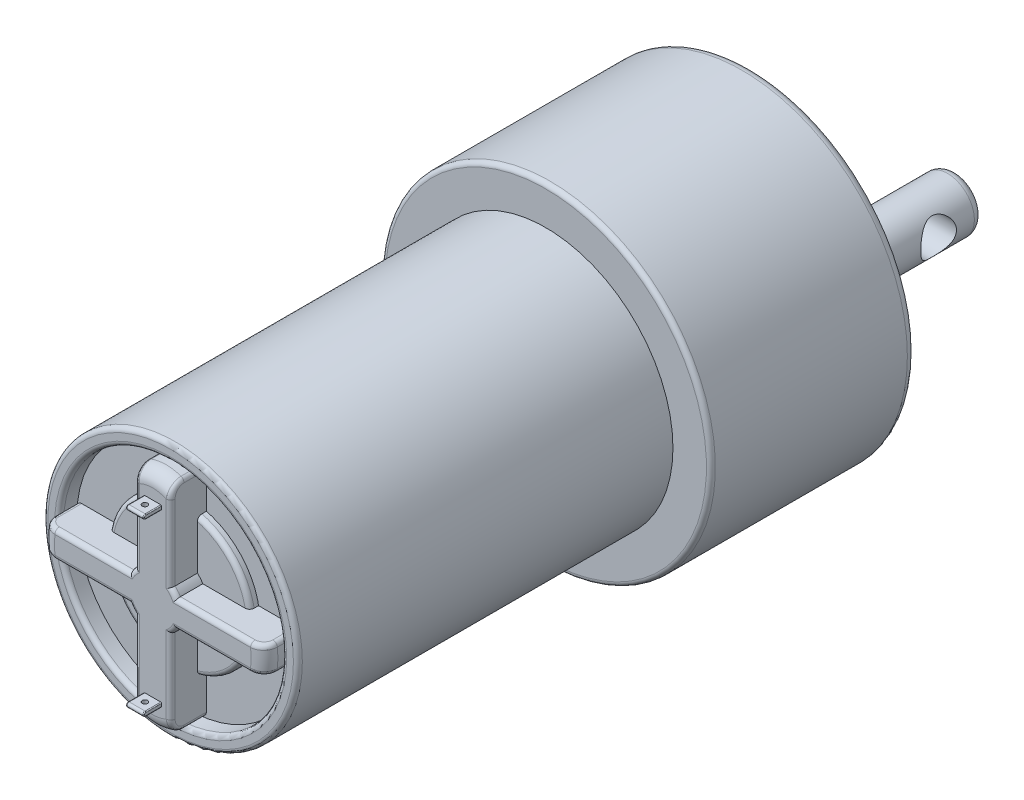
SolidWorks part; units mm, degrees
ref_plane "Front Plane" through (0, 0, 0) normal (0, 0, 1) x (1, 0, 0)
ref_plane "Top Plane" through (0, 0, 0) normal (0, 1, 0) x (1, 0, 0)
ref_plane "Right Plane" through (0, 0, 0) normal (1, 0, 0) x (0, 0, -1)
sketch "Sketch1" plane through (0, 0, 0) normal (0, 0, 1) x (1, 0, 0)
  circle A0 centre (0, 0) radius 14.25
  dimension "D1" = 28.5
extrude "Boss-Extrude1" add sketch "Sketch1" along normal blind 63
sketch "Sketch2" plane through (0, 0, 0) normal (0, 0, -1) x (-1, 0, 0)
  circle A0 centre (0, 0) radius 18.5
  dimension "D1" = 37
extrude "Boss-Extrude2" add sketch "Sketch2" against normal blind 23
sketch "Sketch3" plane through (0, 0, 0) normal (0, 0, -1) x (-1, 0, 0)
  line L0 (0, 0) -> (0, -6)
  line L1 (0, 20.35) -> (0, -20.35) construction
  circle A0 centre (0, -6) radius 6
  dimension "D1" = 6
extrude "Boss-Extrude6" add sketch "Sketch3" along normal blind 8 contours A0 region at (4.1226, -10.1226, 0)
sketch "Sketch6" plane through (0, 0, -8) normal (0, 0, -1) x (-1, 0, 0)
  circle A0 centre (0, -6) radius 3
  dimension "D1" = 6
extrude "Boss-Extrude7" add sketch "Sketch6" along normal blind 15
fillet "Fillet4" radius 1 3 edges at (-3, -6, -23) (-6, -6, -8) (-18.5, 0, 0)
sketch "Sketch7" plane through (0, 0, 63) normal (0, 0, 1) x (1, 0, 0)
  circle A0 centre (0, 0) radius 12.5
  circle A1 centre (0, 0) radius 14.25
  dimension "D1" = 25
extrude "Boss-Extrude8" add sketch "Sketch7" along normal blind 2
sketch "Sketch8" plane through (0, 0, 63) normal (0, 0, 1) x (1, 0, 0)
  circle A0 centre (0, 0) radius 8
  dimension "D1" = 16
extrude "Boss-Extrude9" add sketch "Sketch8" along normal blind 1
sketch "Sketch14" plane through (0, 0, 0) normal (1, 0, 0) x (0, 0, -1)
  circle A0 centre (18, -6) radius 2
  dimension "D2" = 4
extrude "Cut-Extrude2" cut sketch "Sketch14" against normal mid plane 11
sketch "Sketch15" plane through (0, 0, 65) normal (0, 0, 1) x (1, 0, 0)
  line L0 (2, 2.2361) -> (2, 12.0869)
  line L1 (-13.6997, -1.5) -> (-2.5981, -1.5)
  line L2 (-2, -12.0869) -> (-2, -2.2361)
  line L4 (2, -12.0869) -> (2, -2.2361)
  line L5 (-2, 2.2361) -> (-2, 12.0869)
  line L6 (-13.6997, 1.5) -> (-2.5981, 1.5)
  line L8 (0, -1.5) -> (0, -3)
  line L10 (2.5981, 1.5) -> (13.6997, 1.5)
  line L11 (2.5981, -1.5) -> (13.6997, -1.5)
  arc A0 (-2, -12.0869) -> (2, -12.0869) centre (0, -7.452) ccw
  arc A1 (-2, 12.0869) -> (2, 12.0869) centre (0, 7.452) cw
  arc A3 (-13.6997, 1.5) -> (-13.6997, -1.5) centre (-11.9304, 0) ccw
  arc A4 (13.6997, 1.5) -> (13.6997, -1.5) centre (11.9304, 0) cw
  arc A5 (-2, 2.2361) -> (-2.5981, 1.5) centre (0, 0) ccw
  arc A6 (2.5981, 1.5) -> (2, 2.2361) centre (0, 0) ccw
  arc A7 (2, -2.2361) -> (2.5981, -1.5) centre (0, 0) ccw
  arc A8 (-2.5981, -1.5) -> (-2, -2.2361) centre (0, 0) ccw
  point P0 (0, 0)
  point P1 (0, 0)
  dimension "D1" = 6
extrude "Boss-Extrude17" add sketch "Sketch15" along normal mid plane 4 separate body contours L1 A8 L2 A0 L4 A7 L11 L10 A6 L0 A1 L5 A5 L6 region at (0, 0, 65)
fillet "Fillet5" radius 1.5 4 edges at (0, 12.5, 67) (-12.5, 0, 67) (0, -12.5, 67) (12.5, 0, 67)
fillet "Fillet6" radius 0.5 1 edges at (14.25, 0, 65)
fillet "Fillet7" radius 0.5 1 edges at (12.5, 0, 65)
fillet "Fillet8" radius 0.5 1 edges at (8, 0, 64)
fillet "Fillet9" radius 0.5 28 edges at (12.4097, 1.5, 64.25) (11.8485, 1.5, 66.6665) (12.4097, -1.5, 64.25) (12.0827, -1.5, 66.4318) (2, -12.0869, 64.25) (2, -11.5965, 66.5675) (-2, -12.0869, 64.25) (-2, -11.7786, 66.3748) (-12.4097, -1.5, 64.25) (-11.8485, -1.5, 66.6665) (-12.4097, 1.5, 64.25) (-12.0827, 1.5, 66.4318) (-2, 12.0869, 64.25) (-2, 11.5965, 66.5675) (2, 12.0869, 64.25) (2, 11.7786, 66.3748) (2.3283, 1.8918, 67) (6.7477, 1.5, 67) (6.7477, -1.5, 67) (2.3283, -1.8918, 67) (2, -6.3093, 67) (-2, -6.3093, 67) (-2.3283, -1.8918, 67) (-6.7477, -1.5, 67) (-6.7477, 1.5, 67) (-2.3283, 1.8918, 67) (-2, 6.3093, 67) (2, 6.3093, 67)
sketch "Sketch16" plane through (0, 0, 67) normal (0, 0, 1) x (1, 0, 0)
  line L0 (0, -20.35) -> (0, 20.35) construction
  line L1 (0.9853, 9.3193) -> (-0.9853, 9.3193)
  line L2 (0.9853, 9.3193) -> (0.9853, 9.8119)
  line L3 (0.9853, 9.8119) -> (-0.9853, 9.8119)
  line L4 (-0.9853, 9.3193) -> (-0.9853, 9.8119)
  line L5 (0.9853, 9.3193) -> (-0.9853, 9.8119) construction
  line L6 (0.9853, 9.8119) -> (-0.9853, 9.3193) construction
  point P0 (0, 9.5656)
extrude "Boss-Extrude18" add sketch "Sketch16" along normal blind 2 separate body
fillet "Fillet10" 2 edges at (0, 9.3193, 69) (0, 9.8119, 69) type full round first side face at (0, 9.3193, 68) second side face at (0, 9.8119, 68) middle face at (0, 9.5656, 69)
mirror "Mirror1" about plane through (0, 0, 0) normal (0, 1, 0) of bodies 113
fillet "Fillet11" radius 0.5 1 edges at (-18.5, 0, 23)
sketch "Sketch17" plane through (0, 0, 0) normal (0, 0, -1) x (-1, 0, 0)
  line L1 (0, 20.35) -> (0, -20.35) construction
  circle A1 centre (0, -14.5) radius 1.5
  dimension "D2" = 3
extrude "Cut-Extrude4" cut sketch "Sketch17" against normal blind 2
sketch "Sketch18" plane through (0, 0, 2) normal (0, 0, -1) x (-1, 0, 0)
  circle A0 centre (0, -14.5) radius 1.5
curve "Helix/Spiral1" pitch 0.35 height 1.75 radius 1.5 left hand yes centre (0, -14.5, 2) axis (0, 0, -1) start towards (0.7071, 0.7071, 0)
ref_plane "Plane1" through (1.0607, -13.4393, 2) normal (-0.7066, 0.7066, -0.0371) x (0.7076, 0.7056, -0.0371)
sketch "Sketch19" plane through (1.0607, -13.4393, 2) normal (-0.7066, 0.7066, -0.0371) x (0.7076, 0.7056, -0.0371)
  circle A0 centre (0, 0) radius 0.125
  dimension "D1" = 0.25
sweep "Cut-Sweep1" cut profiles "Sketch19" path "Helix/Spiral1" align with end faces yes
pattern_circular "CirPattern1" count 6 over 360 about axis through (0, 0, 0) along (0, 0, -1) of "Cut-Sweep1", "Cut-Extrude4"
sketch "Sketch20" plane through (0, 9.8119, 0) normal (0, 1, 0) x (1, 0, 0)
  circle A0 centre (0, -67.8768) radius 0.3
  dimension "D1" = 0.6
extrude "Cut-Extrude5" cut sketch "Sketch20" against normal blind 70
fillet "Fillet13" radius 0.1 6 edges at (-0.9853, -9.8119, 67.8768) (-0.9853, -9.5656, 69) (-0.9853, -9.3193, 67.8768) (0.9853, -9.5656, 69) (0.9853, -9.8119, 67.8768) (0.9853, -9.3193, 67.8768)
fillet "Fillet14" radius 0.1 6 edges at (0.9853, 9.3193, 67.8768) (0.9853, 9.5656, 69) (-0.9853, 9.3193, 67.8768) (-0.9853, 9.5656, 69) (0.9853, 9.8119, 67.8768) (-0.9853, 9.8119, 67.8768)
